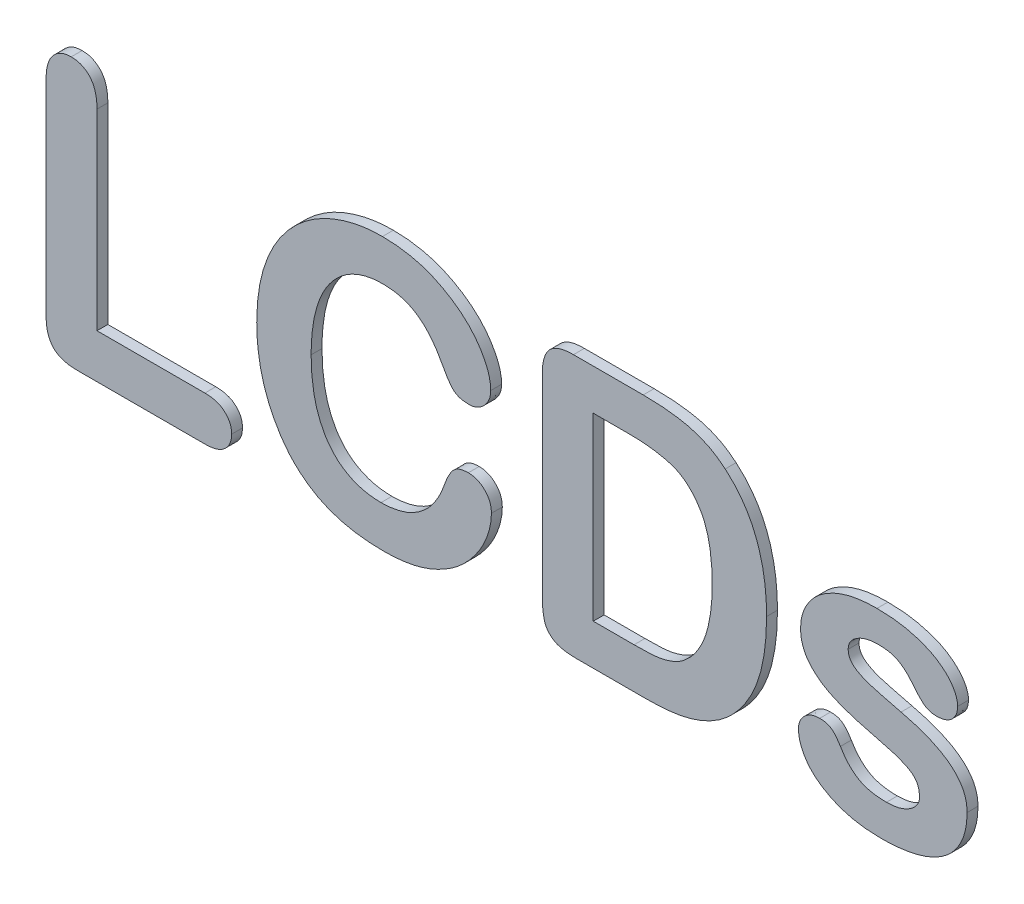
SolidWorks part; units mm, degrees
ref_plane "Front" through (0, 0, 0) normal (0, 0, 1) x (1, 0, 0)
ref_plane "Top" through (0, 0, 0) normal (0, 1, 0) x (1, 0, 0)
ref_plane "Right" through (0, 0, 0) normal (1, 0, 0) x (0, 0, -1)
sketch "Sketch1" plane through (0, 0, 0) normal (0, 0, 1) x (1, 0, 0)
  line L1 (-70.9822, -5) -> (70.9822, -5) construction
  line L2 (-70.9822, -5) -> (-70.9822, 5) construction
  line L3 (-70.9822, 5) -> (70.9822, 5) construction
  line L4 (70.9822, -5) -> (70.9822, 5) construction
  line L5 (-70.9822, -5) -> (70.9822, 5) construction
  line L6 (-70.9822, 5) -> (70.9822, -5) construction
  text T0 "MAXWELL SAVINGS"
  point P0 (0, 0)
  dimension "D1" = 10
extrude "Boss-Extrude1" [suppressed] add sketch "Sketch1" against normal blind 0.99 and the other way blind 0.01
sketch "Sketch2" plane through (0, 0, 0) normal (0, 0, 1) x (1, 0, 0)
  line L1 (-49.8033, -12.5) -> (49.8033, -12.5) construction
  line L2 (-49.8033, -12.5) -> (-49.8033, 12.5) construction
  line L3 (-49.8033, 12.5) -> (49.8033, 12.5) construction
  line L4 (49.8033, -12.5) -> (49.8033, 12.5) construction
  line L5 (-49.8033, -12.5) -> (49.8033, 12.5) construction
  line L6 (-49.8033, 12.5) -> (49.8033, -12.5) construction
  text T0 "LCDs" font "Arial Rounded MT Bold" height 25
  point P0 (0, 0)
  dimension "D1" = 25
extrude "Boss-Extrude2" add sketch "Sketch2" along normal blind 0.01 and the other way blind 0.99
